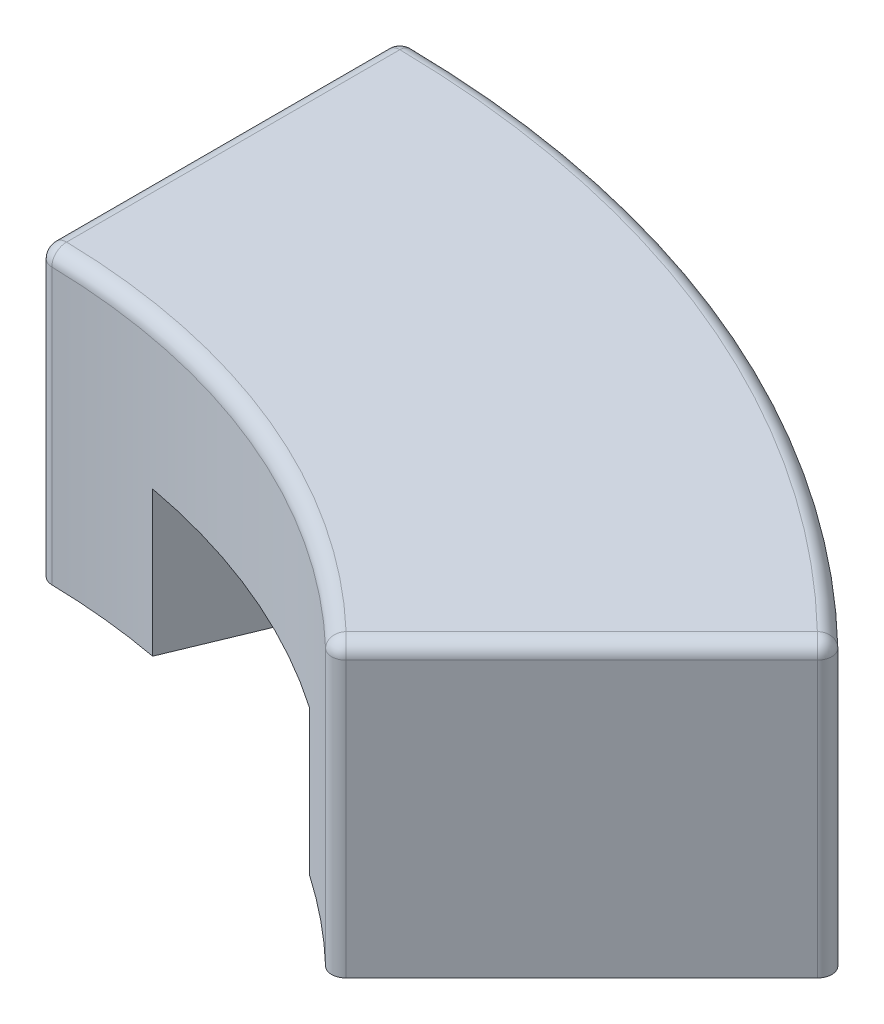
SolidWorks part; units mm, degrees
material "AISI 1020"
ref_plane "Front Plane" through (0, 0, 0) normal (0, 0, 1) x (1, 0, 0)
ref_plane "Top Plane" through (0, 0, 0) normal (0, 1, 0) x (1, 0, 0)
ref_plane "Right Plane" through (0, 0, 0) normal (1, 0, 0) x (0, 0, -1)
sketch "Sketch1" plane through (0, 0, 0) normal (0, 1, 0) x (1, 0, 0)
  line L0 (0, 960) -> (0, 1460)
  line L1 (678.8225, 678.8225) -> (1032.3759, 1032.3759)
  arc A2 (0, 1460) -> (1032.3759, 1032.3759) centre (0, 0) cw
  arc A3 (0, 960) -> (678.8225, 678.8225) centre (0, 0) cw
extrude "Boss-Extrude1" add sketch "Sketch1" along normal blind 400
fillet "Fillet1" radius 20 8 edges at (558.7178, 400, -1348.8641) (1032.3759, 200, -1032.3759) (0, 200, -1460) (0, 400, -1210) (0, 200, -960) (367.3761, 400, -886.9244) (855.5992, 400, -855.5992) (678.8225, 200, -678.8225)
sketch "Sketch3" plane through (0, 400, 0) normal (0, 1, 0) x (1, 0, 0)
  line L1 (0, 0) -> (1417.2815, -587.0572) construction
ref_plane "Plane1" through (0, 0, 0) normal (-0.3827, 0, 0.9239) x (0.9239, 0, 0.3827)
sketch "Sketch4" plane through (0, 0, 0) normal (-0.3827, 0, 0.9239) x (0.9239, 0, 0.3827)
  line L0 (0, 0) -> (200, 0)
  line L1 (-349.1991, 0) -> (349.1991, 0) construction
  line L2 (200, 0) -> (200, 200)
  line L3 (200, 200) -> (-200, 200)
  line L4 (-200, 200) -> (-200, 0)
  line L5 (-200, 0) -> (0, 0)
extrude "Cut-Extrude2" cut sketch "Sketch4" against normal through all
